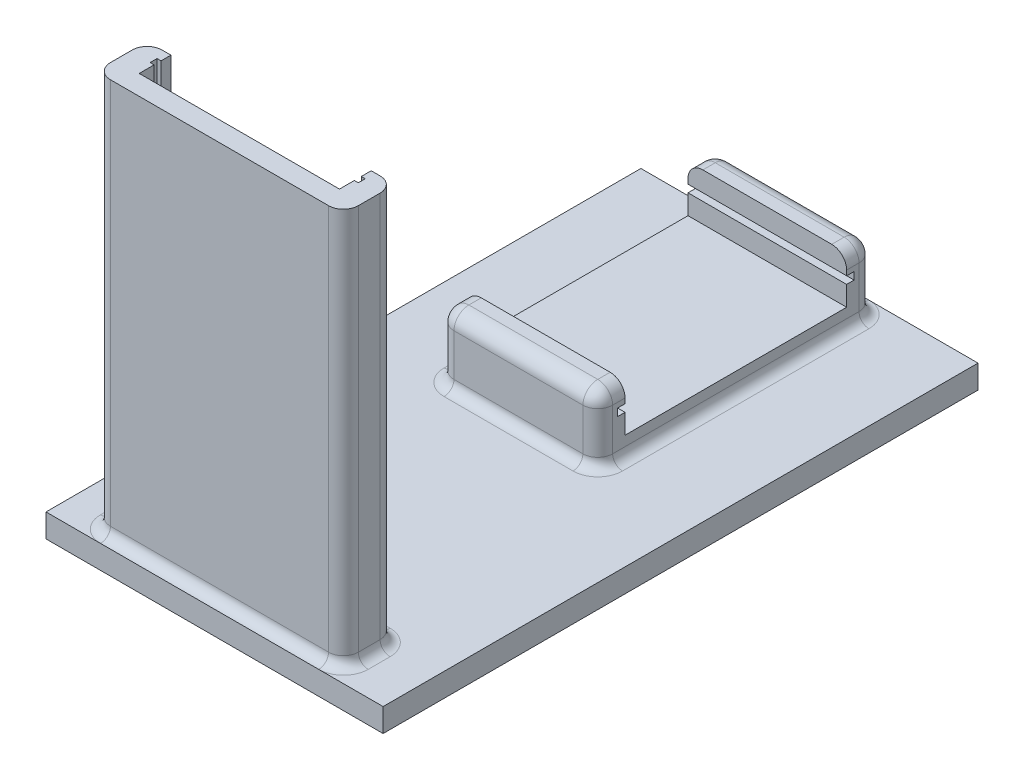
SolidWorks part; units mm, degrees
material "Melamine resin"
ref_plane "Front Plane" through (0, 0, 0) normal (0, 0, 1) x (1, 0, 0)
ref_plane "Top Plane" through (0, 0, 0) normal (0, 1, 0) x (1, 0, 0)
ref_plane "Right Plane" through (0, 0, 0) normal (1, 0, 0) x (0, 0, -1)
sketch "Sketch2" plane through (0, 0, 0) normal (0, 1, 0) x (1, 0, 0)
  line L1 (0, 0) -> (88.9, 0)
  line L2 (0, 0) -> (0, 152.4)
  line L3 (0, 152.4) -> (88.9, 152.4)
  line L10 (88.9, 152.4) -> (88.9, 0)
  dimension "D1" = 152.4
  dimension "D2" = 88.9
extrude "Boss-Extrude1" add sketch "Sketch2" along normal blind 5.9944 contours L3 L10 L1 L2
sketch "Sketch4" plane through (0, 5.9944, 0) normal (0, 1, 0) x (1, 0, 0)
  line L0 (0, 0) -> (0, 152.4) construction
  line L1 (0, 0) -> (88.9, 0) construction
  circle A0 centre (45.72, 109.8713) radius 2.7305
  circle A1 centre (45.72, 33.6713) radius 2.7305
  dimension "D3" = 5.461
  dimension "D4" = 5.461
  dimension "D1" = 76.2
  dimension "D2" = 45.72
  dimension "D5" = 33.6713
extrude "Cut-Extrude2" cut sketch "Sketch4" against normal through all both
sketch "Sketch5" plane through (0, 5.9944, 0) normal (0, 1, 0) x (1, 0, 0)
  line L0 (0, 152.4) -> (88.9, 152.4) construction
  line L1 (12.7, 15.748) -> (76.2, 15.748)
  line L2 (12.7, 15.748) -> (12.7, 2.54)
  line L3 (12.7, 2.54) -> (76.2, 2.54)
  line L4 (76.2, 15.748) -> (76.2, 2.54)
  line L5 (18.796, 7.62) -> (70.104, 7.62)
  line L6 (18.796, 7.62) -> (18.796, 15.748)
  line L7 (18.796, 15.748) -> (70.104, 15.748)
  line L8 (70.104, 7.62) -> (70.104, 15.748)
  line L9 (17.78, 13.208) -> (71.12, 13.208)
  line L10 (17.78, 13.208) -> (17.78, 11.43)
  line L11 (17.78, 11.43) -> (71.12, 11.43)
  line L12 (71.12, 13.208) -> (71.12, 11.43)
  line L13 (0, 0) -> (88.9, 0) construction
  point P12 (71.8842, 128.6711)
  point P13 (79.7243, 141.8754)
  point P16 (44.45, 152.4)
  point P17 (44.45, 15.748)
  point P18 (18.796, 127.6717)
  point P19 (0, 0)
  point P20 (18.796, 129.3154)
  point P21 (18.796, 131.8443)
  dimension "D1" = 53.34
  dimension "D2" = 1.016
  dimension "D3" = 1.016
  dimension "D4" = 3.81
  dimension "D5" = 2.54
  dimension "D6" = 5.08
  dimension "D7" = 5.08
  dimension "D8" = 1.778
  dimension "D9" = 2.54
  dimension "D10" = 5.08
extrude "Boss-Extrude2" add sketch "Sketch5" along normal blind 101.6 contours L9 L12 L11 L8 L5 L6 L10 L1 L2 L3 L4 region at (44.45, 5.9944, -6.5828)
fillet "Fillet1" radius 3.81 4 edges at (12.7, 56.7944, -2.54) (12.7, 56.7944, -15.748) (76.2, 56.7944, -2.54) (76.2, 56.7944, -15.748)
fillet "Fillet2" radius 2.54 9 edges at (17.653, 5.9944, -15.748) (13.8159, 5.9944, -14.6321) (12.7, 5.9944, -9.144) (13.8159, 5.9944, -3.6559) (71.247, 5.9944, -15.748) (75.0841, 5.9944, -14.6321) (76.2, 5.9944, -9.144) (75.0841, 5.9944, -3.6559) (44.45, 5.9944, -2.54)
ref_plane "Plane1" through (44.45, 0, 0) normal (-1, 0, 0) x (0, 0, 1)
sketch "Sketch6" plane through (44.45, 0, 0) normal (-1, 0, 0) x (0, 0, 1)
  line L0 (0, 5.9944) -> (-152.4, 5.9944) construction
  line L1 (0, 5.9944) -> (-152.4, 5.9944)
  line L3 (-149.86, 5.9944) -> (-79.121, 5.9944)
  line L4 (-149.86, 5.9944) -> (-149.86, 23.1394)
  line L5 (-149.86, 23.1394) -> (-79.121, 23.1394)
  line L6 (-79.121, 5.9944) -> (-79.121, 23.1394)
  line L7 (-142.875, 23.1394) -> (-86.106, 23.1394)
  line L8 (-142.875, 23.1394) -> (-142.875, 11.0744)
  line L9 (-142.875, 11.0744) -> (-86.106, 11.0744)
  line L10 (-86.106, 23.1394) -> (-86.106, 11.0744)
  line L11 (-144.78, 18.0594) -> (-84.201, 18.0594)
  line L12 (-144.78, 18.0594) -> (-144.78, 16.1544)
  line L13 (-144.78, 16.1544) -> (-84.201, 16.1544)
  line L14 (-84.201, 18.0594) -> (-84.201, 16.1544)
  line L15 (-152.4, 5.9944) -> (-152.4, 0) construction
  point P16 (0, 0)
  dimension "D1" = 60.579
  dimension "D2" = 1.905
  dimension "D3" = 1.905
  dimension "D4" = 1.905
  dimension "D5" = 5.08
  dimension "D6" = 5.08
  dimension "D7" = 5.08
  dimension "D8" = 5.08
  dimension "D9" = 5.08
  dimension "D10" = 2.54
extrude "Boss-Extrude3" add sketch "Sketch6" along normal mid plane 40.64 contours L11 L14 L13 L10 L9 L8 L12 L5 L4 L1 L6 region at (44.45, 6.7223, -114.4905)
fillet "Fillet3" radius 3.81 2 edges at (44.45, 23.1394, -79.121) (44.45, 23.1394, -149.86)
fillet "Fillet6" radius 3.81 12 edges at (24.13, 23.1394, -84.5185) (24.13, 22.0235, -80.2369) (64.77, 23.1394, -84.5185) (64.77, 22.0235, -80.2369) (64.77, 23.1394, -144.4625) (64.77, 22.0235, -148.7441) (24.13, 23.1394, -144.4625) (24.13, 22.0235, -148.7441) (24.13, 12.6619, -79.121) (64.77, 12.6619, -79.121) (64.77, 12.6619, -149.86) (24.13, 12.6619, -149.86)
fillet "Fillet7" radius 2.54 8 edges at (25.2459, 5.9944, -80.2369) (44.45, 5.9944, -79.121) (63.6541, 5.9944, -80.2369) (64.77, 5.9944, -114.4905) (63.6541, 5.9944, -148.7441) (44.45, 5.9944, -149.86) (25.2459, 5.9944, -148.7441) (24.13, 5.9944, -114.4905)
sketch "Sketch7" plane through (0, 5.9944, 0) normal (0, 1, 0) x (1, 0, 0)
  line L0 (0, 0) -> (16.51, 0) construction
  line L1 (0, 152.4) -> (2.54, 152.4)
  line L2 (0, 152.4) -> (0, 0)
  line L3 (0, 0) -> (2.54, 0)
  line L4 (2.54, 152.4) -> (2.54, 0)
  dimension "D1" = 2.54
extrude "Cut-Extrude3" cut sketch "Sketch7" against normal through all both
equation "\"threaded_insert_hole\"=0.1472"
equation "\"th\"=1.25249"
